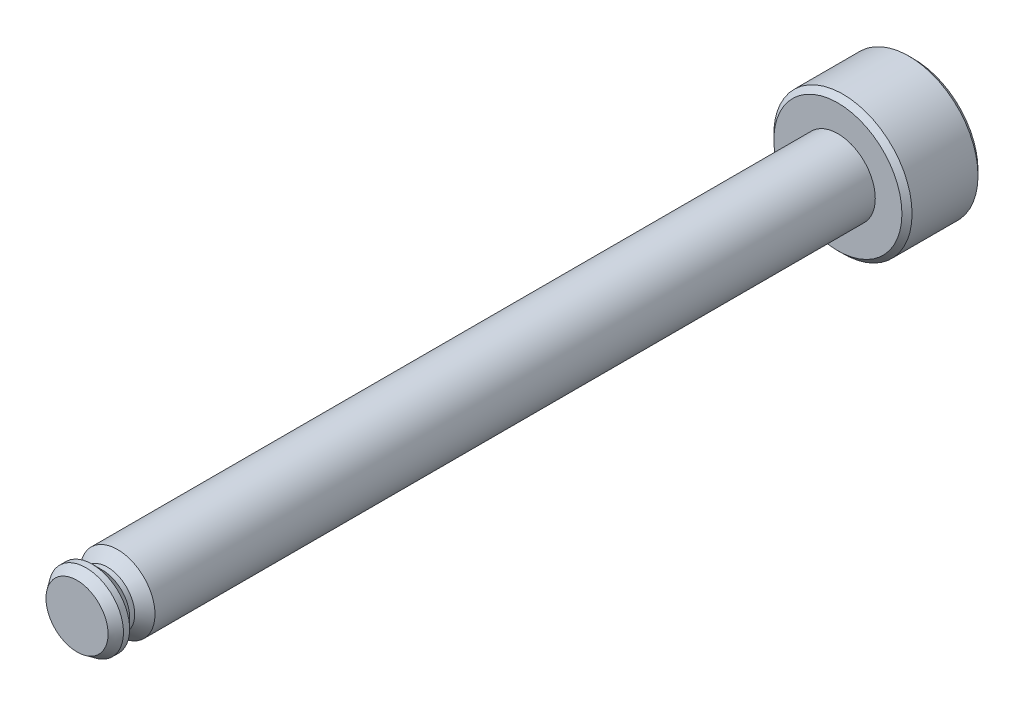
SolidWorks part; units mm, degrees
ref_plane "Front" through (0, 0, 0) normal (0, 0, 1) x (1, 0, 0)
ref_plane "Top" through (0, 0, 0) normal (0, 1, 0) x (1, 0, 0)
ref_plane "Right" through (0, 0, 0) normal (1, 0, 0) x (0, 0, -1)
sketch "Sketch2" plane through (0, 0, 0) normal (0, 0, 1) x (1, 0, 0)
  circle A0 centre (0, 0) radius 1.475
  dimension "D1" = 2.95
extrude "Shaft" add sketch "Sketch2" along normal blind 30
sketch "Sketch5" plane through (0, 0, 0) normal (0, 0, 1) x (1, 0, 0)
  circle A0 centre (0, 0) radius 2.725
  dimension "D1" = 5.45
extrude "Head" add sketch "Sketch5" against normal blind 3
sketch "Sketch4" plane through (0, 0, 0) normal (1, 0, 0) x (0, 0, -1)
  line L0 (0, 0) -> (-54.4, 0) construction
  line L1 (-54.4, 0) -> (-54.4, 4.3666) construction
  line L2 (-54.9, 1.475) -> (-53.9, 1.475)
  line L3 (0, 1.475) -> (-30, 1.475) construction
  line L6 (-53.9, 1.475) -> (-54.3, 1.075)
  line L7 (-54.3, 1.075) -> (-54.5, 1.075)
  line L8 (-54.5, 1.075) -> (-54.9, 1.475)
  line L10 (-54.4, 56.7809) -> (-54.4, -43.2191) construction
  dimension "D2" = 1
  dimension "D3" = 45
  dimension "D4" = 0.4
revolve "e-Clip Notch Short" [suppressed] cut sketch "Sketch4" angle 360 about L0
chamfer "Chamfer1" distance 0.25 angle 55 1 edges at (1.475, 0, 30) first distance on face at (1.475, 0, 30)
chamfer "Deburs" distance 0.2 angle 45 2 edges at (2.725, 0, 0) (2.725, 0, -3)
sketch "Sketch6" plane through (0, 0, 0) normal (1, 0, 0) x (0, 0, -1)
  line L0 (0, 0) -> (-28.9, 0) construction
  line L1 (-28.9, 0) -> (-28.9, 1.075) construction
  line L2 (0, 1.475) -> (-29.643, 1.475) construction
  line L3 (-29.4, 1.475) -> (-28.4, 1.475)
  line L4 (-28.4, 1.475) -> (-28.8, 1.075)
  line L5 (-28.8, 1.075) -> (-29, 1.075)
  line L6 (-29, 1.075) -> (-29.4, 1.475)
  line L7 (-28.9, 1.075) -> (-28.9, 1.475) construction
  line L8 (-54.9, 1.475) -> (-53.9, 1.475) construction
  line L9 (-54.5, 1.075) -> (-54.9, 1.475) construction
  line L10 (-28.9, 50) -> (-28.9, -50) construction
revolve "e-Clip Notch Long" cut sketch "Sketch6" angle 360 about L0
equation "\"D1@Sketch2\"=\"Plastic Hardware OD@Box Assy.Assembly\""
equation "\"D1@Sketch5\"=\"Hardware Head Countersink Diameter@Box Assy.Assembly\"-.3mm"
equation "\"D1@Head\"=\"Countersink Depth@Box Assy.Assembly\""
